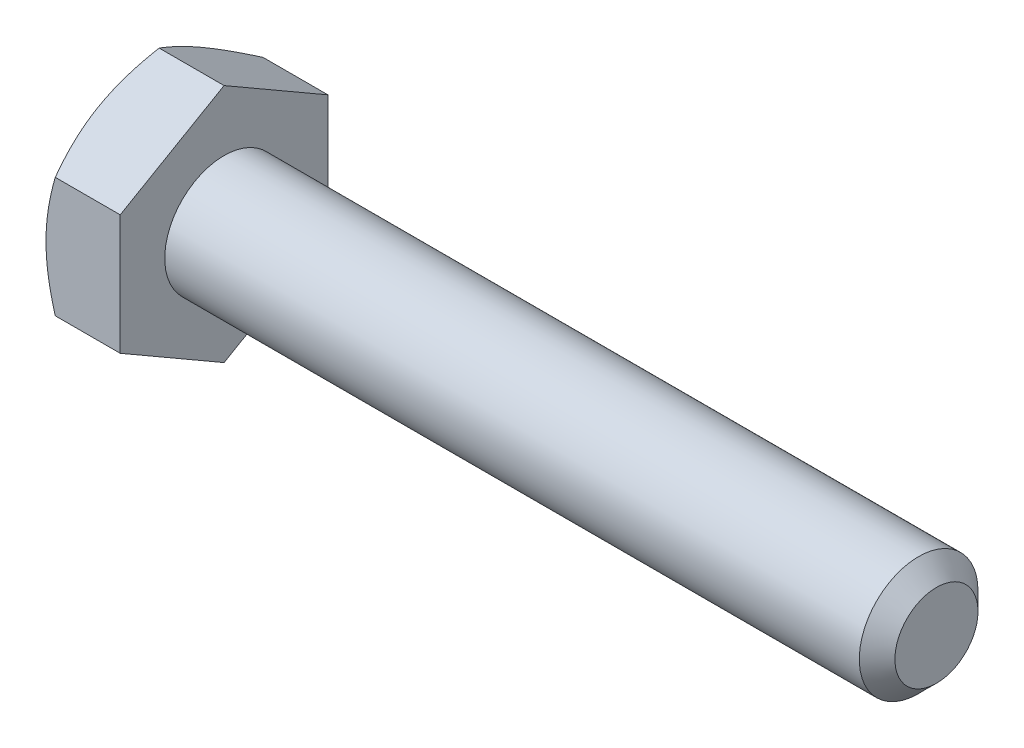
SolidWorks part; units mm, degrees
material "6061-T6 (SS)"
ref_plane "Front Plane" through (0, 0, 0) normal (0, 0, 1) x (1, 0, 0)
ref_plane "Top Plane" through (0, 0, 0) normal (0, 1, 0) x (1, 0, 0)
ref_plane "Right Plane" through (0, 0, 0) normal (1, 0, 0) x (0, 0, -1)
sketch "Sketch1" plane through (0, 0, 0) normal (0, 0, 1) x (1, 0, 0)
  line L0 (-21.0344, 0) -> (21.0344, 0) construction
  line L1 (21.0344, 3.175) -> (21.0344, -3.175) construction
  line L2 (-17.0656, 5.5562) -> (-17.0656, -5.5562) construction
  line L3 (-21.0344, 5.5562) -> (-21.0344, -5.5562) construction
  line L4 (22.225, -3.3125) -> (21.59, -2.2126) construction
  line L5 (21.59, -2.2126) -> (20.955, -3.3125) construction
  line L6 (20.955, -3.3125) -> (22.225, -3.3125) construction
  line L7 (22.1456, -3.175) -> (21.0344, -3.175) construction
  line L8 (21.59, -3.3125) -> (21.59, -3.175) construction
  line L9 (21.59, -3.175) -> (21.59, -2.3501) construction
  line L10 (21.59, -2.3501) -> (21.59, -2.2126) construction
  line L15 (21.6694, -2.3501) -> (21.5106, -2.3501)
  line L16 (22.1853, -3.2437) -> (20.9947, -3.2437)
  line L17 (21.5106, -2.3501) -> (20.9947, -3.2437)
  line L18 (21.6694, -2.3501) -> (22.1853, -3.2437)
  point P9 (-17.0656, 0)
  point P10 (16.0955, -3.175)
  point P24 (21.59, -3.2437)
  dimension "Head Ht" = 3.9688
  dimension "D1" = 4.9389
  dimension "Pitch" = 1.27
  dimension "D3" = 0.1588
  dimension "Head Width" = 11.1125
  dimension "Length" = 38.1
  dimension "Screw Size" = 6.35
ref_plane "Plane2" through (21.0344, 0, 0) normal (1, 0, 0) x (0, 0, -1)
sketch "Sketch5" plane through (21.0344, 0, 0) normal (1, 0, 0) x (0, 0, -1)
  circle A0 centre (0, 0) radius 3.175
extrude "Boss-Extrude3" add sketch "Sketch5" against normal up to vertex (38.1 mm away) up to point (-17.0656, 0, 0)
chamfer "Chamfer1" distance 0.9525 angle 45 1 edges at (21.0344, 0, -3.175)
sketch "Sketch6" plane through (-17.0656, 0, 0) normal (-1, 0, 0) x (0, 0, 1)
  line L0 (0, 5.5562) -> (0, -5.5562) construction
  line L1 (5.5562, 3.2079) -> (0, 6.4158)
  line L2 (0, 6.4158) -> (-5.5563, 3.2079)
  line L3 (-5.5563, 3.2079) -> (-5.5562, -3.2079)
  line L4 (-5.5562, -3.2079) -> (0, -6.4158)
  line L5 (0, -6.4158) -> (5.5563, -3.2079)
  line L6 (5.5563, -3.2079) -> (5.5562, 3.2079)
  circle A0 centre (0, 0) radius 5.5562 construction
extrude "Boss-Extrude4" add sketch "Sketch6" along normal up to vertex (3.9688 mm away) up to point (-21.0344, -5.5562, 0)
sketch "Sketch7" plane through (-21.0344, 0, 0) normal (-1, 0, 0) x (0, 0, 1)
  circle A0 centre (0, 0) radius 5.5562 construction
  circle A1 centre (0, 0) radius 5.5562
sketch "Sketch8" plane through (-21.0344, 0, 0) normal (-1, 0, 0) x (0, 0, 1)
  circle A0 centre (0, 0) radius 5.5562 construction
  circle A1 centre (0, 0) radius 5.5562
extrude "Cut-Extrude3" cut sketch "Sketch8" against normal through all draft 60 flip side to cut
split "Split1" [suppressed] bodies to split 113
sketch "Sketch9" [suppressed] plane through (21.0344, 0, 0) normal (1, 0, 0) x (0, 0, -1)
  circle A0 centre (0, 0) radius 3.175 construction
  circle A1 centre (0, 0) radius 3.175
curve "Helix/Spiral1" [suppressed] pitch 1.27 height 39.37 turns 31
sketch "Sketch10" [suppressed] plane through (0, 0, 0) normal (0, 0, 1) x (1, 0, 0)
  line L8 (21.6694, -2.3501) -> (21.5106, -2.3501) construction
  line L9 (21.5106, -2.3501) -> (20.9947, -3.2437) construction
  line L10 (22.1853, -3.2437) -> (20.9947, -3.2437) construction
  line L11 (21.6694, -2.3501) -> (22.1853, -3.2437) construction
  line L12 (21.6694, -2.3501) -> (21.5106, -2.3501)
  line L13 (21.5106, -2.3501) -> (20.9947, -3.2437)
  line L14 (22.1853, -3.2437) -> (20.9947, -3.2437)
  line L15 (21.6694, -2.3501) -> (22.1853, -3.2437)
sweep "Cut-Sweep1" [suppressed] cut profiles "Sketch10" path "Helix/Spiral1"
combine bodies "Combine1" [suppressed] operation type add bodies to combine 119 120
sketch "Sketch11" [suppressed] plane through (-17.0656, 0, 0) normal (1, 0, 0) x (0, 0, -1)
  line L0 (0, 5.5562) -> (0, -5.5562) construction
  circle A0 centre (0, 0) radius 3.4925
  point P3 (0, -3.4925)
  dimension "D1" = 0.3175
extrude "Boss-Extrude5" [suppressed] add sketch "Sketch11" along normal through all draft 45
equation "\"D3@Helix/Spiral1\"= \"Length@Sketch1\" + \"Pitch@Sketch1\""
equation "\"D1@Chamfer1\" = \"Pitch@Sketch1\" * .75"
equation "\"D4@Helix/Spiral1\"=\"Pitch@Sketch1\""
equation "\"D3@Sketch1\" = \"Pitch@Sketch1\" / 8"
equation "\"D1@Sketch11\"=\"Pitch@Sketch1\"/4"
